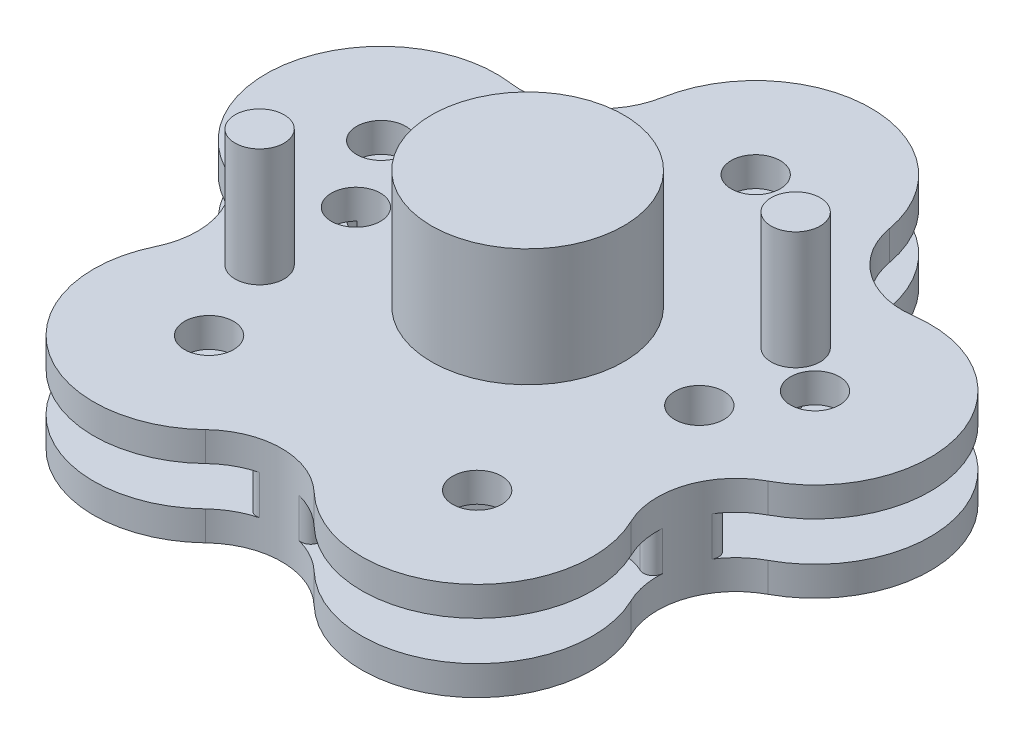
SolidWorks part; units mm, degrees
ref_plane "Front Plane" through (0, 0, 0) normal (0, 0, 1) x (1, 0, 0)
ref_plane "Top Plane" through (0, 0, 0) normal (0, 1, 0) x (1, 0, 0)
ref_plane "Right Plane" through (0, 0, 0) normal (1, 0, 0) x (0, 0, -1)
sketch "Croquis1" plane through (0, 0, 0) normal (0, 1, 0) x (1, 0, 0)
  line L0 (-13.6636, -18.8064) -> (-22.1082, 7.1834) construction
  line L1 (-22.1082, 7.1834) -> (0, 23.246) construction
  line L2 (0, 23.246) -> (22.1082, 7.1834) construction
  line L3 (22.1082, 7.1834) -> (13.6636, -18.8064) construction
  line L4 (13.6636, -18.8064) -> (-13.6636, -18.8064) construction
  line L5 (0, 0) -> (0, 23.246) construction
  line L6 (-58.9442, 35) -> (49.3844, 35) construction
  line L7 (-13.6636, -18.8064) -> (0, 0) construction
  line L8 (0, 0) -> (13.6636, -18.8064) construction
  arc A0 (11.5676, 25.3314) -> (-11.5676, 25.3314) centre (0, 23.246) ccw
  arc A1 (-24.2478, -13.6943) -> (-5.5311, -27.2928) centre (-13.6636, -18.8064) ccw
  arc A3 (27.6662, -3.1736) -> (20.517, 18.8292) centre (22.1082, 7.1834) ccw
  arc A4 (-20.517, 18.8292) -> (-27.6662, -3.1736) centre (-22.1082, 7.1834) ccw
  arc A5 (-24.2478, -13.6943) -> (-27.6662, -3.1736) centre (-31.4462, -10.2175) ccw
  arc A6 (-20.517, 18.8292) -> (-11.5676, 25.3314) centre (-19.4348, 26.7498) ccw
  arc A7 (11.5676, 25.3314) -> (20.517, 18.8292) centre (19.4348, 26.7498) ccw
  arc A8 (27.6662, -3.1736) -> (24.2478, -13.6943) centre (31.4462, -10.2175) ccw
  arc A9 (5.5311, -27.2928) -> (-5.5311, -27.2928) centre (0, -33.0645) ccw
  arc A10 (5.5311, -27.2928) -> (24.2478, -13.6943) centre (13.6636, -18.8064) ccw
  dimension "D7" = 35
  dimension "D1" = 108
  dimension "D2" = 108
  dimension "D3" = 108
  dimension "D4" = 108
  dimension "D5" = 108
extrude "Saliente-Extruir1" add sketch "Croquis1" along normal blind 10
sketch "Croquis2" plane through (0, 10, 0) normal (0, 1, 0) x (1, 0, 0)
  circle A0 centre (-22.1082, 7.1834) radius 2.5
  circle A1 centre (0, 23.246) radius 2.5
  circle A2 centre (22.1082, 7.1834) radius 2.5
  circle A3 centre (13.6636, -18.8064) radius 2.5
  circle A4 centre (-13.6636, -18.8064) radius 2.5
  arc A7 (-20.517, 18.8292) -> (-27.6662, -3.1736) centre (-22.1082, 7.1834) ccw construction
  arc A8 (11.5676, 25.3314) -> (-11.5676, 25.3314) centre (0, 23.246) ccw construction
  arc A9 (27.6662, -3.1736) -> (20.517, 18.8292) centre (22.1082, 7.1834) ccw construction
  arc A10 (5.5311, -27.2928) -> (24.2478, -13.6943) centre (13.6636, -18.8064) ccw construction
  arc A11 (-24.2478, -13.6943) -> (-5.5311, -27.2928) centre (-13.6636, -18.8064) ccw construction
  dimension "D1" = 5
extrude "Cortar-Extruir1" cut sketch "Croquis2" against normal blind 10
sketch "Croquis3" plane through (0, 10, 0) normal (0, 1, 0) x (1, 0, 0)
  circle A0 centre (0, 0) radius 9.8
  dimension "D1" = 19.6
extrude "Saliente-Extruir2" add sketch "Croquis3" along normal blind 12
sketch "Croquis4" plane through (0, 0, 0) normal (1, 0, 0) x (0, 0, -1)
  line L0 (18.8292, 10) -> (18.8292, 0) construction
  line L1 (18.8292, 7) -> (36.4827, 7)
  line L2 (18.8292, 7) -> (18.8292, 3)
  line L3 (18.8292, 3) -> (36.4827, 3)
  line L4 (36.4827, 7) -> (36.4827, 3)
  line L5 (35, 10) -> (25.3314, 10) construction
  line L6 (25.3314, 0) -> (35, 0) construction
  dimension "D1" = 3
  dimension "D2" = 3
extrude "Cortar-Extruir2" cut sketch "Croquis4" against normal mid plane 23
sketch "Croquis5" plane through (11.5, 0, 0) normal (-1, 0, 0) x (0, 0, 1)
  line L1 (-25.6765, 7) -> (-22.444, 7)
  line L2 (-25.6765, 7) -> (-25.6765, 3)
  line L3 (-25.6765, 3) -> (-22.444, 3)
  line L4 (-22.444, 7) -> (-22.444, 3)
extrude "Cortar-Extruir3" cut sketch "Croquis5" against normal through all both and the other way through all
fillet "Redondeo1" radius 1 4 edges at (11.5, 5, -22.444) (12.6994, 5, -22.444) (-12.6994, 5, -22.444) (-11.5, 5, -22.444)
fillet "Redondeo2" radius 5 2 edges at (-11.5, 5, -18.8292) (11.5, 5, -18.8292)
sketch "Croquis6" plane through (0, 0, 0) normal (1, 0, 0) x (0, 0, -1)
  line L0 (0, 0) -> (0, 41.0079) construction
pattern_circular "MatrizC7" count 5 every 72 about axis through (0, 0, 0) along (0, 1, 0) of "Cortar-Extruir2"
fillet "Redondeo3" radius 1 8 edges at (-20.8661, 5, -18.8716) (-27.9735, 5, 3.0027) (-24.3959, 5, 14.0132) (-5.7886, 5, 27.5322) (5.7886, 5, 27.5322) (24.3959, 5, 14.0132) (27.9735, 5, 3.0027) (20.8661, 5, -18.8716)
fillet "Redondeo4" radius 5 8 edges at (14.354, 5, -16.7557) (21.4614, 5, 5.1186) (20.3712, 5, 8.4736) (1.7639, 5, 21.9927) (-1.7639, 5, 21.9927) (-20.3712, 5, 8.4736) (-21.4614, 5, 5.1186) (-14.354, 5, -16.7557)
sketch "Croquis7" plane through (0, 0, 0) normal (0, -1, 0) x (1, 0, 0)
  line L0 (-3.1694, 0) -> (0, 0) construction
  line L1 (-10.0921, 13.1691) -> (-3.1694, 13.1691)
  line L2 (-10.0921, 13.1691) -> (-10.0921, -13.1691)
  line L3 (-10.0921, -13.1691) -> (-3.1694, -13.1691)
  line L4 (-3.1694, 13.1691) -> (-3.1694, -13.1691)
  line L5 (3.6698, 13.1691) -> (10.5925, 13.1691)
  line L6 (3.6698, 13.1691) -> (3.6698, -13.1691)
  line L7 (3.6698, -13.1691) -> (10.5925, -13.1691)
  line L8 (10.5925, 13.1691) -> (10.5925, -13.1691)
extrude "Cortar-Extruir4" cut sketch "Croquis7" against normal blind 6 and the other way through all
fillet "Redondeo5" radius 3 6 edges at (-6.6307, 6, 13.1691) (-6.6307, 6, -13.1691) (7.1312, 6, -13.1691) (7.1312, 6, 13.1691) (3.6698, 6, 0) (-3.1694, 6, 0)
sketch "Croquis9" plane through (0, 22, 0) normal (0, 1, 0) x (1, 0, 0)
  line L0 (-17.5, 0) -> (17.5, 0) construction
  circle A0 centre (0, 0) radius 17.5 construction
  circle A1 centre (17.5, 0) radius 2.5
  circle A2 centre (-17.5, 0) radius 2.5
  dimension "D1" = 35
  dimension "D2" = 5
extrude "Cortar-Extruir5" cut sketch "Croquis9" against normal blind 22
sketch "Croquis10" plane through (0, 10, 0) normal (0, 1, 0) x (1, 0, 0)
  circle A0 centre (0, 0) radius 17.5 construction
  circle A1 centre (17.3205, 10) radius 2.5
  circle A2 centre (-17.5, 0) radius 2.5 construction
  circle A3 centre (17.5, 0) radius 2.5 construction
  circle A4 centre (-17.3205, -10) radius 2.5
  dimension "D1" = 35
  dimension "D2" = 10
  dimension "D3" = 10
  dimension "D4" = 5
extrude "Saliente-Extruir3" add sketch "Croquis10" along normal blind 12
